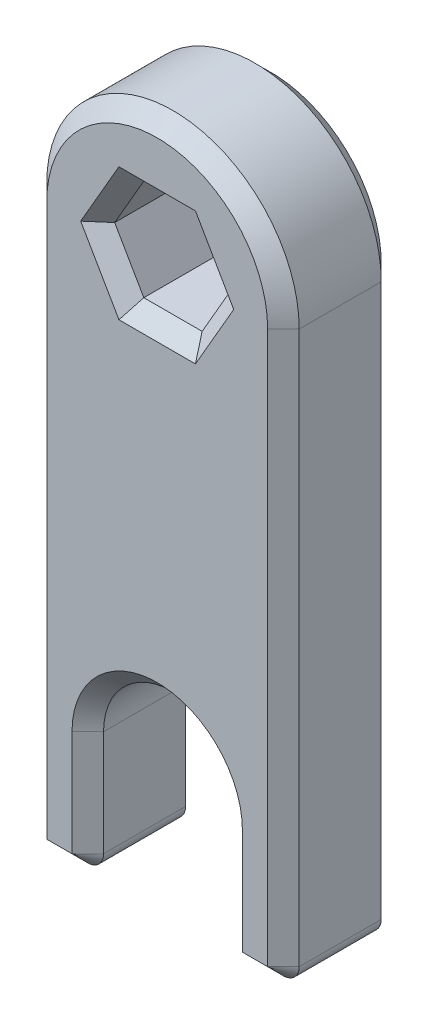
SolidWorks part; units mm, degrees
ref_plane "Front Plane" through (0, 0, 0) normal (0, 0, 1) x (1, 0, 0)
ref_plane "Top Plane" through (0, 0, 0) normal (0, 1, 0) x (1, 0, 0)
ref_plane "Right Plane" through (0, 0, 0) normal (1, 0, 0) x (0, 0, -1)
ref_plane "Plane1" through (0, 0, 0) normal (0, 0, -1) x (-1, 0, 0)
sketch "Sketch1" plane through (0, 0, 0) normal (0, 0, -1) x (-1, 0, 0)
  line L0 (-4, 14) -> (-4, 4)
  line L1 (-4, 4) -> (4, 4)
  line L2 (4, 4) -> (4, 14)
  line L19 (-0.9238, 12.4) -> (-1.8475, 14)
  line L20 (-1.8475, 14) -> (-0.9238, 15.6)
  line L21 (-0.9238, 15.6) -> (0.9238, 15.6)
  line L22 (0.9238, 15.6) -> (1.8475, 14)
  line L23 (1.8475, 14) -> (0.9238, 12.4)
  line L24 (0.9238, 12.4) -> (-0.9238, 12.4)
  arc A0 (4, 14) -> (-4, 14) centre (0, 14) ccw
extrude "Boss-Extrude1" add sketch "Sketch1" against normal blind 3.6
sketch "Sketch6" plane through (0, 0, 0) normal (0, 0, -1) x (-1, 0, 0)
  line L0 (-4, -4) -> (-2.2, -4)
  line L1 (-2.2, -4) -> (-2.2, -0.15)
  line L2 (-2.2, -4) -> (2.2, -4) construction
  line L3 (-4, 14) -> (-4, 4) construction
  line L4 (-4, 4) -> (4, 4) construction
  line L8 (2.2, -0.15) -> (2.2, -4)
  line L9 (2.2, -4) -> (4, -4)
  line L10 (4, -4) -> (4, 4)
  line L11 (4, 4) -> (-4, 4)
  line L12 (-4, 4) -> (-4, -4)
  arc A0 (2.2, -0.15) -> (-2.2, -0.15) centre (0, -0.15) ccw
  dimension "D3" = 4.15
  dimension "D4" = 2.2
  dimension "D1" = 8
  dimension "D2" = 8
extrude "Boss-Extrude2" add sketch "Sketch6" against normal blind 3.6
fillet "Fillet1" radius 0.5 4 edges at (4, -4, 1.8) (2.2, -4, 1.8) (-4, -4, 1.8) (-2.2, -4, 1.8)
chamfer "Chamfer1" distance 0.5 angle 45 36 edges at (0, 18, 0) (-4, 5.25, 0) (-3.8536, -3.8536, 0) (-3.1, -4, 0) (-2.3464, -3.8536, 0) (-2.2, -1.825, 0) (0, 2.05, 0) (2.2, -1.825, 0) (2.3464, -3.8536, 0) (3.1, -4, 0) (3.8536, -3.8536, 0) (4, 5.25, 0) (-1.3856, 13.2, 0) (-1.3856, 14.8, 0) (0, 15.6, 0) (1.3856, 14.8, 0) (1.3856, 13.2, 0) (0, 12.4, 0) (2.3464, -3.8536, 3.6) (2.2, -1.825, 3.6) (0, 2.05, 3.6) (-2.2, -1.825, 3.6) (-2.3464, -3.8536, 3.6) (-3.1, -4, 3.6) (-3.8536, -3.8536, 3.6) (-4, 5.25, 3.6) (0, 18, 3.6) (4, 5.25, 3.6) (3.8536, -3.8536, 3.6) (3.1, -4, 3.6) (1.3856, 14.8, 3.6) (0, 15.6, 3.6) (-1.3856, 14.8, 3.6) (-1.3856, 13.2, 3.6) (0, 12.4, 3.6) (1.3856, 13.2, 3.6)
ref_plane "Plane2" through (0, 0, 1.8) normal (0, 0, -1) x (-1, 0, 0)
